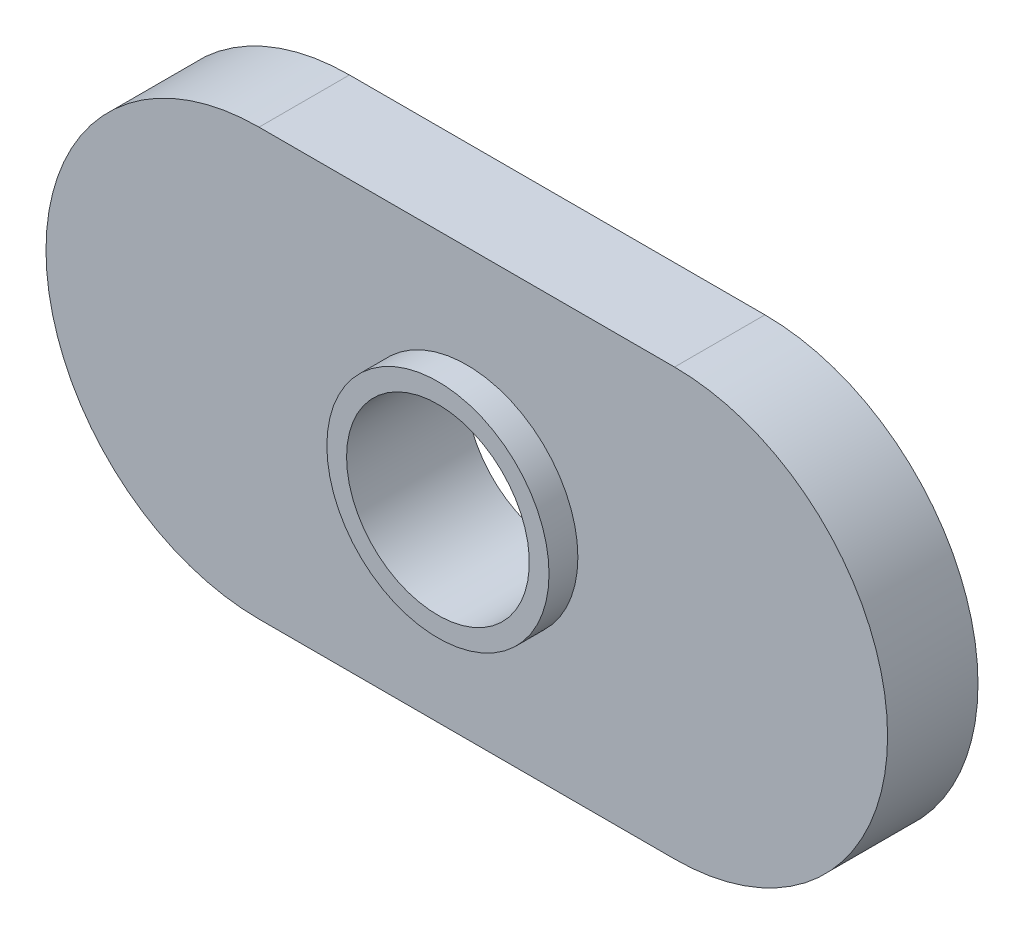
SolidWorks part; units mm, degrees
material "AISI 1020"
ref_plane "Front Plane" through (0, 0, 0) normal (0, 0, 1) x (1, 0, 0)
ref_plane "Top Plane" through (0, 0, 0) normal (0, 1, 0) x (1, 0, 0)
ref_plane "Right Plane" through (0, 0, 0) normal (1, 0, 0) x (0, 0, -1)
sketch "Sketch1" plane through (0, 0, 0) normal (0, 0, 1) x (1, 0, 0)
  line L0 (105.6526, 125.9331) -> (127.8776, 125.9331) construction
  line L88 (111.2787, 131.5592) -> (122.2515, 131.5592)
  line L89 (111.2787, 120.307) -> (122.2515, 120.307)
  arc A0 (111.2787, 120.307) -> (111.2787, 131.5592) centre (111.2787, 125.9331) cw
  arc A1 (122.2515, 120.307) -> (122.2515, 131.5592) centre (122.2515, 125.9331) ccw
  point P4 (105.6526, 125.9331)
  dimension "D1" = 11.2522
  dimension "D2" = 22.225
extrude "Extrude1" add sketch "Sketch1" along normal blind 2.3876
sketch "Sketch4" plane through (0, 0, 2.3876) normal (0, 0, 1) x (1, 0, 0)
  line L1 (105.6526, 125.9331) -> (127.8776, 125.9331) construction
  circle A0 centre (116.7651, 125.9331) radius 2.9337
  arc A1 (111.2787, 131.5592) -> (111.2787, 120.307) centre (111.2787, 125.9331) ccw construction
  arc A2 (122.2515, 120.307) -> (122.2515, 131.5592) centre (122.2515, 125.9331) ccw construction
  dimension "D1" = 5.8674
extrude "Extrude3" add sketch "Sketch4" along normal blind 0.762
sketch "Sketch6" plane through (0, 0, 0) normal (0, 0, -1) x (-1, 0, 0)
  circle A0 centre (-116.7651, 125.9331) radius 2.413
  dimension "D1" = 4.826
extrude "Cut-Extrude1" cut sketch "Sketch6" against normal through all
